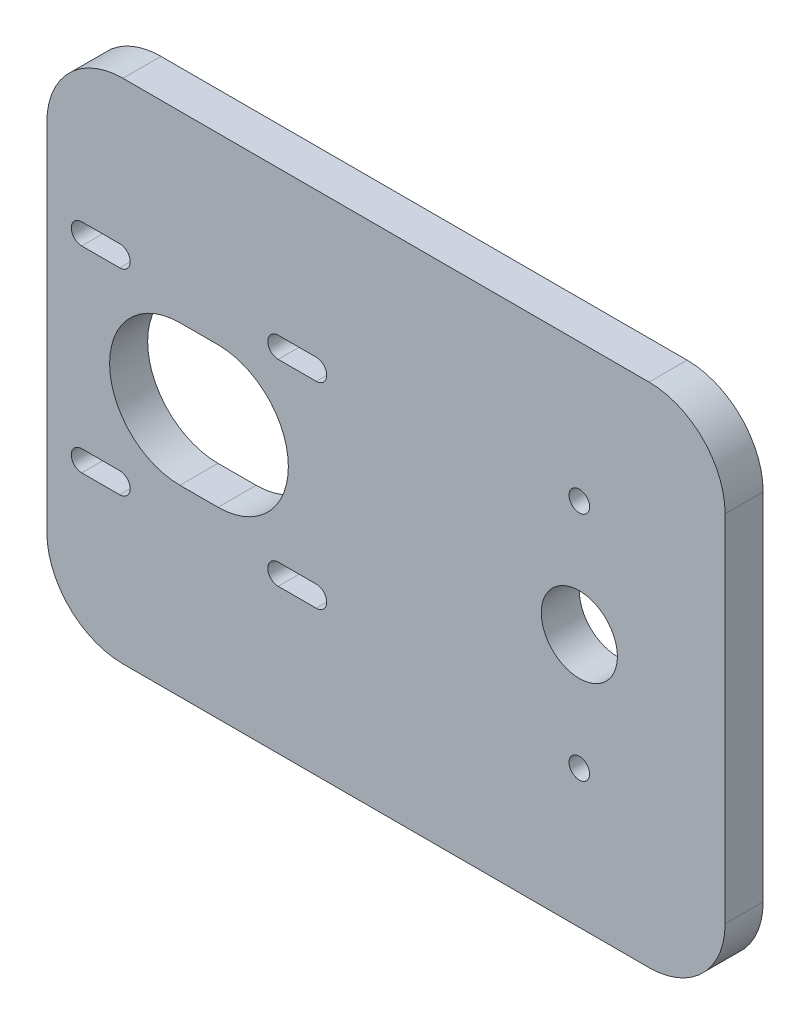
SolidWorks part; units mm, degrees
ref_plane "Alzado" through (0, 0, 0) normal (0, 0, 1) x (1, 0, 0)
ref_plane "Planta" through (0, 0, 0) normal (0, 1, 0) x (1, 0, 0)
ref_plane "Vista lateral" through (0, 0, 0) normal (1, 0, 0) x (0, 0, -1)
sketch "Croquis1" plane through (0, 0, 0) normal (0, 0, 1) x (1, 0, 0)
  line L1 (0, 0) -> (107, 0)
  line L2 (0, 0) -> (0, 80)
  line L3 (0, 80) -> (107, 80)
  line L4 (107, 0) -> (107, 80)
  dimension "D1" = 80
  dimension "D2" = 107
extrude "Saliente-Extruir1" add sketch "Croquis1" along normal blind 6
sketch "Croquis2" plane through (0, 0, 0) normal (0, 0, -1) x (-1, 0, 0)
  line L0 (0, 80) -> (0, 0) construction
  line L1 (0, 40) -> (-107, 40) construction
  line L4 (-107, 0) -> (-107, 80) construction
  line L7 (-21, 40) -> (-27, 40) construction
  line L10 (-21, 28.9) -> (-27, 28.9)
  line L19 (-21, 51.1) -> (-27, 51.1)
  line L20 (-5.5, 24.5) -> (-11.5, 24.5) construction
  line L21 (-5.5, 22.85) -> (-11.5, 22.85)
  line L22 (-5.5, 26.15) -> (-11.5, 26.15)
  line L23 (-36.5, 55.5) -> (-42.5, 55.5) construction
  line L24 (-36.5, 53.85) -> (-42.5, 53.85)
  line L25 (-36.5, 57.15) -> (-42.5, 57.15)
  line L26 (-36.5, 24.5) -> (-42.5, 24.5) construction
  line L27 (-36.5, 22.85) -> (-42.5, 22.85)
  line L28 (-36.5, 26.15) -> (-42.5, 26.15)
  line L29 (-5.5, 55.5) -> (-11.5, 55.5) construction
  line L30 (-5.5, 53.85) -> (-11.5, 53.85)
  line L31 (-5.5, 57.15) -> (-11.5, 57.15)
  line L32 (-84, 0) -> (-84, 80) construction
  line L33 (0, 0) -> (-107, 0) construction
  line L34 (-107, 80) -> (0, 80) construction
  line L35 (-53, 0) -> (-53, 80) construction
  circle A5 centre (-84, 40) radius 6
  circle A15 centre (-84, 21.75) radius 1.625
  circle A16 centre (-84, 58.25) radius 1.625
  arc A19 (-21, 28.9) -> (-21, 51.1) centre (-21, 40) ccw
  arc A20 (-27, 51.1) -> (-27, 28.9) centre (-27, 40) ccw
  arc A21 (-5.5, 22.85) -> (-5.5, 26.15) centre (-5.5, 24.5) ccw
  arc A22 (-11.5, 26.15) -> (-11.5, 22.85) centre (-11.5, 24.5) ccw
  arc A23 (-36.5, 53.85) -> (-36.5, 57.15) centre (-36.5, 55.5) ccw
  arc A24 (-42.5, 57.15) -> (-42.5, 53.85) centre (-42.5, 55.5) ccw
  arc A25 (-36.5, 22.85) -> (-36.5, 26.15) centre (-36.5, 24.5) ccw
  arc A26 (-42.5, 26.15) -> (-42.5, 22.85) centre (-42.5, 24.5) ccw
  arc A27 (-5.5, 53.85) -> (-5.5, 57.15) centre (-5.5, 55.5) ccw
  arc A28 (-11.5, 57.15) -> (-11.5, 53.85) centre (-11.5, 55.5) ccw
  point P6 (-24, 40)
  point P19 (-8.5, 24.5)
  point P28 (-39.5, 55.5)
  point P35 (-39.5, 24.5)
  point P48 (-8.5, 55.5)
  dimension "D2" = 6
  dimension "D3" = 11.1
  dimension "D4" = 3.3
  dimension "D5" = 6
  dimension "D6" = 12
  dimension "D13" = 3.25
  dimension "D14" = 3.25
  dimension "D7" = 15.5
  dimension "D8" = 15.5
  dimension "D9" = 3.3
  dimension "D10" = 6
  dimension "D11" = 23
  dimension "D12" = 40
  dimension "D15" = 18.25
  dimension "D16" = 18.25
  dimension "D17" = 3.3
  dimension "D18" = 6
  dimension "D19" = 3.3
  dimension "D20" = 6
  dimension "D21" = 15.5
  dimension "D22" = 15.5
  dimension "D23" = 15.5
  dimension "D24" = 15.5
  dimension "D25" = 15.5
  dimension "D26" = 15.5
  dimension "D27" = 60
  dimension "D28" = 26
extrude "Cortar-Extruir1" cut sketch "Croquis2" against normal through all
fillet "Redondeo1" radius 12 4 edges at (107, 0, 3) (107, 80, 3) (0, 0, 3) (0, 80, 3)
